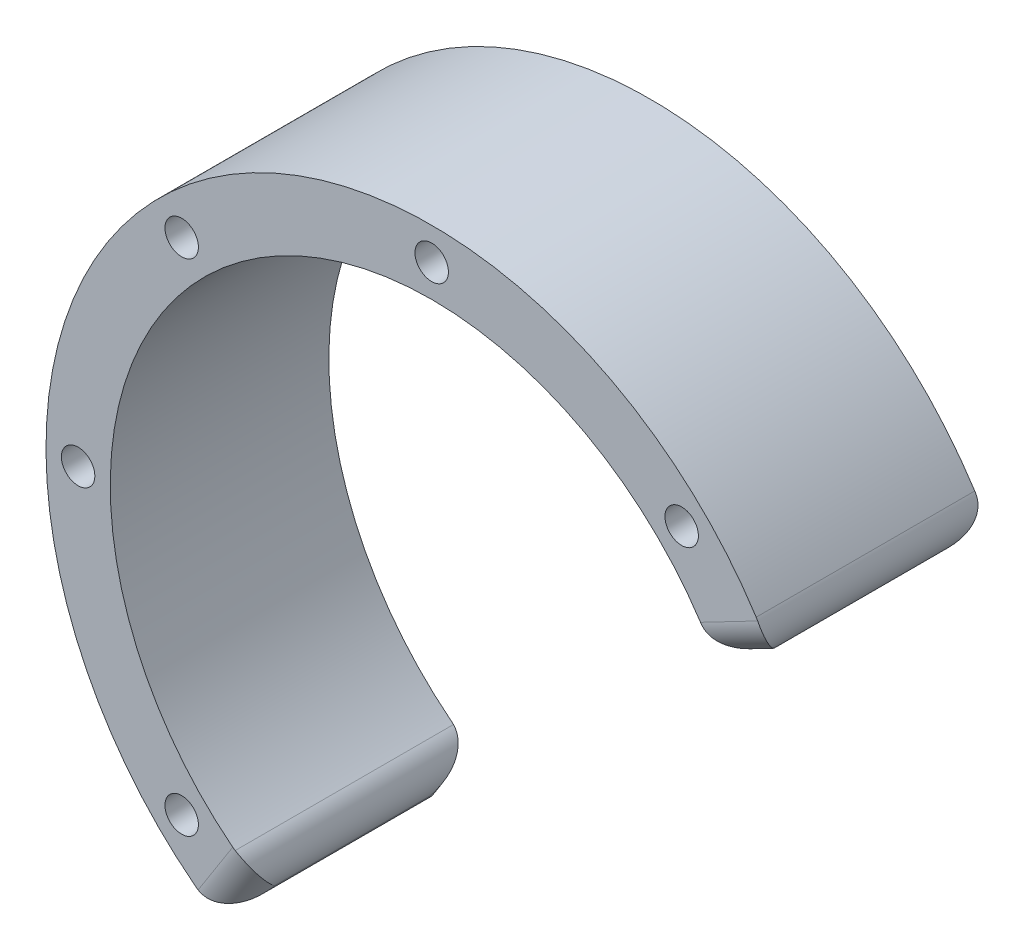
SolidWorks part; units mm, degrees
ref_plane "前视基准面" through (0, 0, 0) normal (0, 0, 1) x (1, 0, 0)
ref_plane "上视基准面" through (0, 0, 0) normal (0, 1, 0) x (1, 0, 0)
ref_plane "右视基准面" through (0, 0, 0) normal (1, 0, 0) x (0, 0, -1)
other "Configuration Table"
sketch "草图2" plane through (0, 0, 0) normal (0, 0, 1) x (1, 0, 0)
  circle A0 centre (0, 0) radius 55 construction
  circle A1 centre (0, 55) radius 2.6
  circle A2 centre (38.8909, 38.8909) radius 2.6
  circle A3 centre (55, 0) radius 2.6
  circle A4 centre (38.8909, -38.8909) radius 2.6
  circle A5 centre (0, -55) radius 2.6
  circle A6 centre (-38.8909, -38.8909) radius 2.6
  circle A7 centre (-55, 0) radius 2.6
  circle A8 centre (-38.8909, 38.8909) radius 2.6
  circle A9 centre (0, 0) radius 50
  circle A10 centre (0, 0) radius 60
  point P21 (0, 0)
  dimension "D1" = 110
  dimension "D2" = 5.2
  dimension "D4" = 100
  dimension "D5" = 120
  dimension "D3" = 8
extrude "凸台-拉伸1" add sketch "草图2" along normal blind 34
sketch "草图3" plane through (0, 0, 34) normal (0, 0, 1) x (1, 0, 0)
  line L0 (0, 0) -> (0, 64.8134) construction
  line L1 (0, 0) -> (40.2212, 63.1346) construction
  line L2 (0, 0) -> (53.2206, 27.7049)
  line L3 (0, 0) -> (-32.238, -50.6035)
  circle A0 centre (0, 0) radius 50 construction
  circle A1 centre (0, 0) radius 60
  circle A2 centre (0, 0) radius 60
  circle A3 centre (0, 0) radius 50
  circle A4 centre (0, 0) radius 60 construction
  point P2 (0, 0)
  point P5 (0, 0)
  point P12 (-22.961, -55.4328)
  circle M8 centre (38.8909, -38.8909) radius 2.6
  circle M10 centre (0, 0) radius 60
  circle M12 centre (55, 0) radius 2.6
  circle M13 centre (0, -55) radius 2.6
  circle M15 centre (0, 0) radius 50
  dimension "D1" = 32.5
  dimension "D2" = 30
  dimension "D3" = 0
extrude "切除-拉伸1" cut sketch "草图3" against normal blind 34 contours L3 L2 M15 M10 M8 M12 M13 region at (49.3733, 24.2672, 34)
fillet "圆角1" radius 5 8 edges at (53.2206, 27.7049, 17) (48.7856, 25.3962, 0) (44.3505, 23.0874, 17) (48.7856, 25.3962, 34) (-26.865, -42.1696, 17) (-29.5515, -46.3865, 0) (-32.238, -50.6035, 17) (-29.5515, -46.3865, 34)
